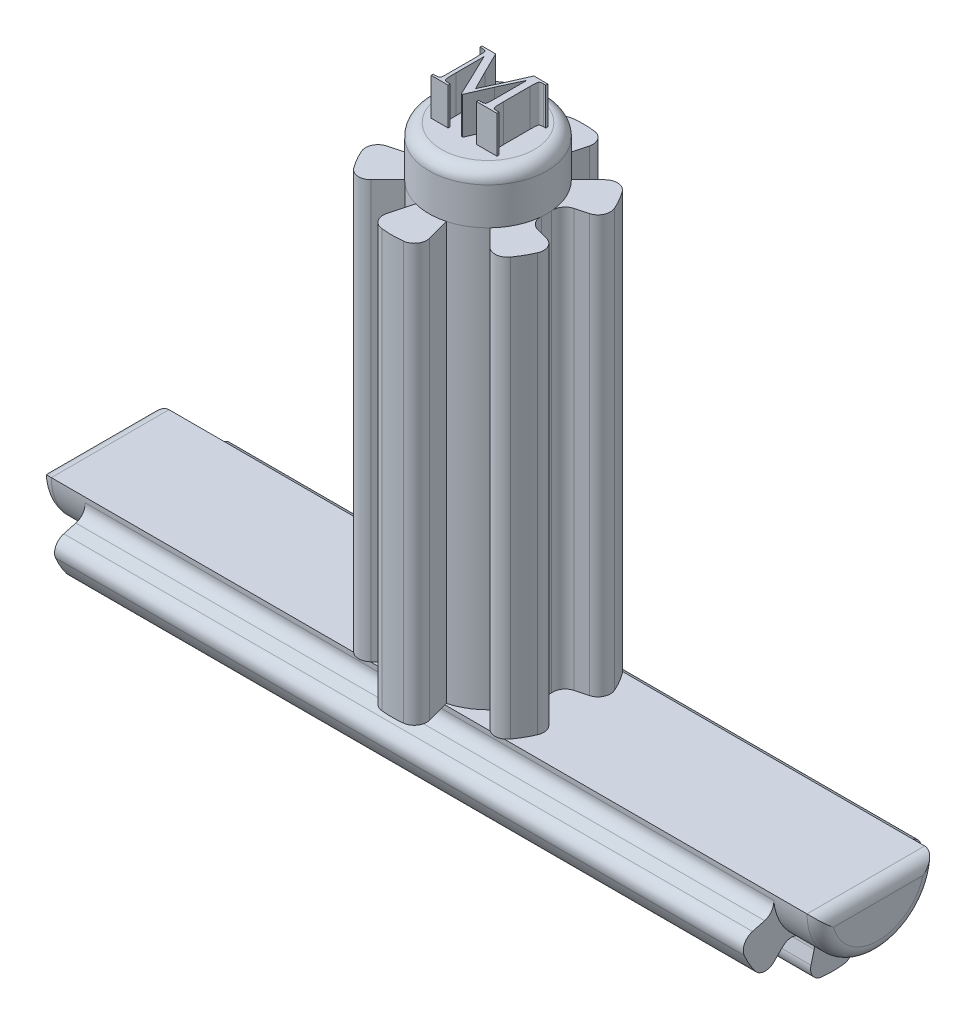
SolidWorks part; units mm, degrees
ref_plane "Front Plane" through (0, 0, 0) normal (0, 0, 1) x (1, 0, 0)
ref_plane "Top Plane" through (0, 0, 0) normal (0, 1, 0) x (1, 0, 0)
ref_plane "Right Plane" through (0, 0, 0) normal (1, 0, 0) x (0, 0, -1)
sketch "Sketch1" plane through (0, 0, 0) normal (0, 1, 0) x (1, 0, 0)
  line L3 (-1.6794, 1.6794) -> (-2.74, 2.74)
  line L5 (-1.6794, -1.6794) -> (-2.74, -2.74)
  line L8 (0.6147, -2.2941) -> (1.0029, -3.743)
  line L9 (-0.6147, -2.2941) -> (-1.0029, -3.743)
  line L11 (-0.6147, 2.2941) -> (-1.0029, 3.743)
  line L12 (0.6147, 2.2941) -> (1.0029, 3.743)
  line L15 (-2.2941, 0.6147) -> (-3.743, 1.0029)
  line L16 (-2.2941, -0.6147) -> (-3.743, -1.0029)
  line L18 (1.7174, -1.6405) -> (2.7779, -2.7017)
  line L19 (2.2941, -0.6147) -> (3.743, -1.0029)
  line L20 (2.2941, 0.6147) -> (3.743, 1.0029)
  line L21 (1.6794, 1.6794) -> (2.74, 2.74)
  arc A0 (-2.74, 2.74) -> (-3.743, 1.0029) centre (0, 0) ccw
  arc A1 (-0.6147, 2.2941) -> (-1.6794, 1.6794) centre (0, 0) ccw
  arc A2 (0.6147, -2.2941) -> (1.7174, -1.6405) centre (0, 0) ccw
  arc A3 (-2.2941, 0.6147) -> (-2.2941, -0.6147) centre (0, 0) ccw
  arc A4 (-1.6794, -1.6794) -> (-0.6147, -2.2941) centre (0, 0) ccw
  arc A5 (2.2941, -0.6147) -> (2.2941, 0.6147) centre (0, 0) ccw
  arc A6 (1.6794, 1.6794) -> (0.6147, 2.2941) centre (0, 0) ccw
  arc A7 (1.0029, 3.743) -> (-1.0029, 3.743) centre (0, 0) ccw
  arc A8 (3.743, 1.0029) -> (2.74, 2.74) centre (0, 0) ccw
  arc A9 (2.7779, -2.7017) -> (3.743, -1.0029) centre (0, 0) ccw
  arc A10 (-1.0029, -3.743) -> (1.0029, -3.743) centre (0, 0) ccw
  arc A11 (-3.743, -1.0029) -> (-2.74, -2.74) centre (0, 0) ccw
  dimension "D2" = 3.875
  dimension "D3" = 2.375
  dimension "D10" = 30
  dimension "D11" = 30
  dimension "D14" = 30
  dimension "D15" = 30
extrude "Boss-Extrude1" add sketch "Sketch1" along normal blind 16.85
sketch "Sketch2" plane through (0, 16.85, 0) normal (0, 1, 0) x (1, 0, 0)
  circle A0 centre (0, 0) radius 2.38
extrude "Boss-Extrude2" add sketch "Sketch2" along normal blind 2
ref_plane "Plane5" through (13.9, 0, 0) normal (1, 0, 0) x (0, 0, -1)
sketch "Sketch10" plane through (13.9, 0, 0) normal (1, 0, 0) x (0, 0, -1)
  line L0 (-2.375, 0) -> (2.375, 0)
  line L1 (-2.2941, -0.6147) -> (-3.743, -1.0029)
  line L2 (2.2941, -0.6147) -> (3.743, -1.0029)
  line L3 (-1.6794, -1.6794) -> (-2.74, -2.74)
  line L4 (1.6794, -1.6794) -> (2.74, -2.74)
  line L5 (-0.6147, -2.2941) -> (-1.0029, -3.743)
  line L6 (0.6147, -2.2941) -> (1.0029, -3.743)
  arc A0 (-3.743, -1.0029) -> (-2.74, -2.74) centre (0, 0) ccw
  arc A1 (-2.375, 0) -> (-2.2941, -0.6147) centre (0, 0) ccw
  arc A2 (2.2941, -0.6147) -> (2.375, 0) centre (0, 0) ccw
  arc A3 (0.6147, -2.2941) -> (1.6794, -1.6794) centre (0, 0) ccw
  arc A4 (-1.6794, -1.6794) -> (-0.6147, -2.2941) centre (0, 0) ccw
  arc A5 (-1.0029, -3.743) -> (1.0029, -3.743) centre (0, 0) ccw
  arc A6 (2.74, -2.74) -> (3.743, -1.0029) centre (0, 0) ccw
  arc A7 (-2.375, 0) -> (2.375, 0) centre (0, 0) ccw
  dimension "D1" = 3.875
  dimension "D2" = 2.375
  dimension "D5" = 15
  dimension "D6" = 15
  dimension "D7" = 30
  dimension "D8" = 30
extrude "Boss-Extrude9" add sketch "Sketch10" against normal blind 31.5 from offset 1.85 contours A1 A7 A4 A3 A2 L0 region at (13.9, -1.008, 0)
extrude "Boss-Extrude10" add sketch "Sketch10<3>" against normal blind 27.8 contours A7 L4 A6 L2 | A7 L5 A5 L6 | A7 L1 A0 L3 region at (13.9, -1.5744, 2.7269) region at (13.9, -1.5744, -2.7269) region at (13.9, -3.1487, 0)
sketch "Sketch10<3>" plane through (13.9, 0, 0) normal (1, 0, 0) x (0, 0, -1) same geometry as "Sketch10"
fillet "Fillet4" radius 0.5 31 edges at (0, 18.85, 2.38) (-1.0029, 8.425, 3.743) (1.0029, 8.425, 3.743) (2.7779, 8.425, 2.7017) (3.743, 8.425, 1.0029) (2.2941, 8.425, 0.6147) (2.2941, 8.425, -0.6147) (3.743, 8.425, -1.0029) (2.74, 8.425, -2.74) (1.0029, 8.425, -3.743) (-1.0029, 8.425, -3.743) (-2.74, 8.425, -2.74) (-3.743, 8.425, -1.0029) (-2.74, 8.425, 2.74) (-3.743, 8.425, 1.0029) (-15.75, 0, 0) (-15.75, -2.375, 0) (15.75, 0, 0) (15.75, -2.375, 0) (0, -0.6147, -2.2941) (0, -1.0029, -3.743) (0, -2.74, -2.74) (0, -1.6794, -1.6794) (0, -2.2941, -0.6147) (0, -3.743, -1.0029) (0, -3.743, 1.0029) (0, -2.2941, 0.6147) (0, -1.6794, 1.6794) (0, -2.74, 2.74) (0, -0.6147, 2.2941) (0, -1.0029, 3.743)
sketch "Sketch11" plane through (0, 18.85, 0) normal (0, 1, 0) x (1, 0, 0)
  text T0 "M" font "Book Antiqua" height in points 8
extrude "Boss-Extrude11" add sketch "Sketch11" along normal blind 1.5
